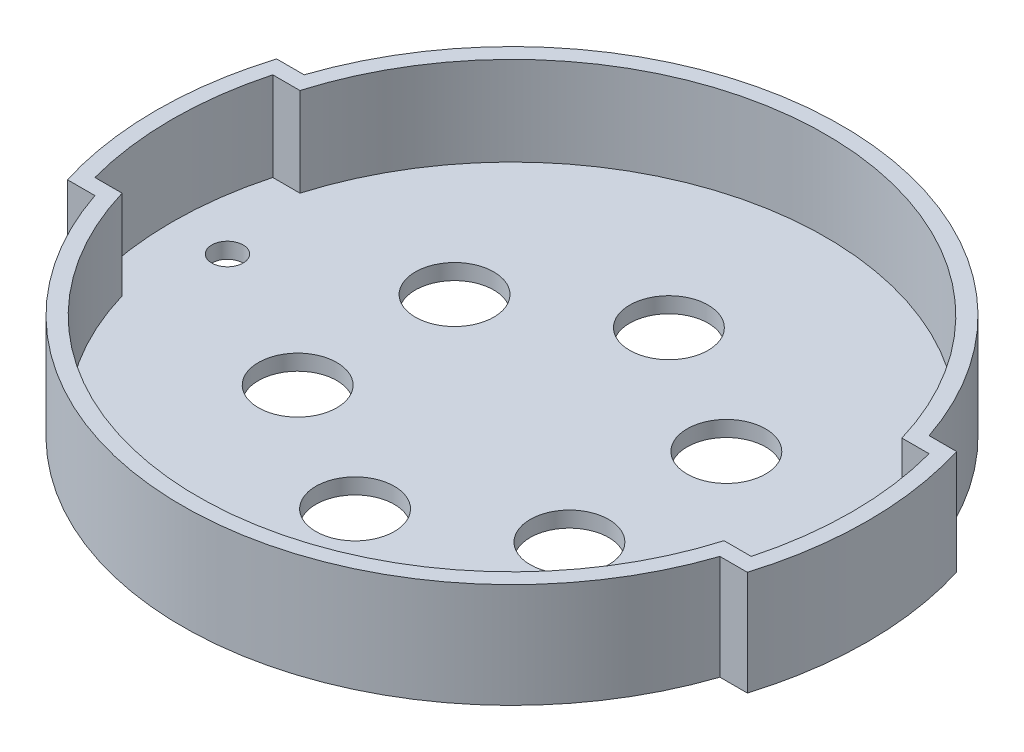
SolidWorks part; units mm, degrees
ref_plane "Front Plane" through (0, 0, 0) normal (0, 0, 1) x (1, 0, 0)
ref_plane "Top Plane" through (0, 0, 0) normal (0, 1, 0) x (1, 0, 0)
ref_plane "Right Plane" through (0, 0, 0) normal (1, 0, 0) x (0, 0, -1)
sketch "Sketch1" plane through (0, 0, 0) normal (0, 1, 0) x (1, 0, 0)
  circle A0 centre (0, 0) radius 68
  dimension "D1" = 136
extrude "Boss-Extrude1" add sketch "Sketch1" along normal blind 20
sketch "Sketch2" plane through (0, 20, 0) normal (0, 1, 0) x (1, 0, 0)
  line L1 (0, 37.0764) -> (0, -27.4787) construction
  line L5 (-59.7411, -20) -> (-64.9923, -20)
  line L6 (-59.7411, 20) -> (-64.9923, 20)
  line L7 (59.7411, -20) -> (64.9923, -20)
  line L8 (59.7411, 20) -> (64.9923, 20)
  line L9 (-28.4675, 0) -> (19.3594, 0) construction
  arc A0 (-59.7411, -20) -> (59.7411, -20) centre (0, 0) ccw
  arc A1 (-64.9923, -20) -> (64.9923, -20) centre (0, 0) ccw
  circle A2 centre (0, 0) radius 68 construction
  arc A3 (59.7411, 20) -> (-59.7411, 20) centre (0, 0) ccw
  arc A4 (64.9923, 20) -> (-64.9923, 20) centre (0, 0) ccw
  dimension "D1" = 126
  dimension "D2" = 40
  dimension "D3" = 40
extrude "Cut-Extrude1" cut sketch "Sketch2" against normal up to surface (20 mm away) up to face at (0, 0, 68)
shell "Shell1" thickness 3 removed face at (0, 20, 0)
sketch "Sketch3" plane through (0, 0, 0) normal (0, -1, 0) x (1, 0, 0)
  line L0 (-78.2757, 0) -> (93.912, 0) construction
  line L1 (0, -33.8158) -> (0, 27.4106) construction
  circle A0 centre (-54.4, 0) radius 3
  circle A1 centre (54.4, 0) radius 3
  circle A2 centre (0, 30) radius 7.5
  circle A3 centre (25.9808, 15) radius 7.5
  circle A4 centre (25.9808, -15) radius 7.5
  circle A5 centre (0, -30) radius 7.5
  circle A6 centre (-25.9808, -15) radius 7.5
  circle A7 centre (-25.9808, 15) radius 7.5
  point P11 (0, 0)
  point P12 (0, -27.599)
  point P24 (0, 0)
  dimension "D1" = 6
  dimension "D2" = 6
  dimension "D5" = 15
  dimension "D3" = 54.4
  dimension "D4" = 54.4
  dimension "D6" = 30
  dimension "D8" = 30
  dimension "D7" = 6
extrude "Cut-Extrude2" cut sketch "Sketch3" against normal through all both and the other way through all
